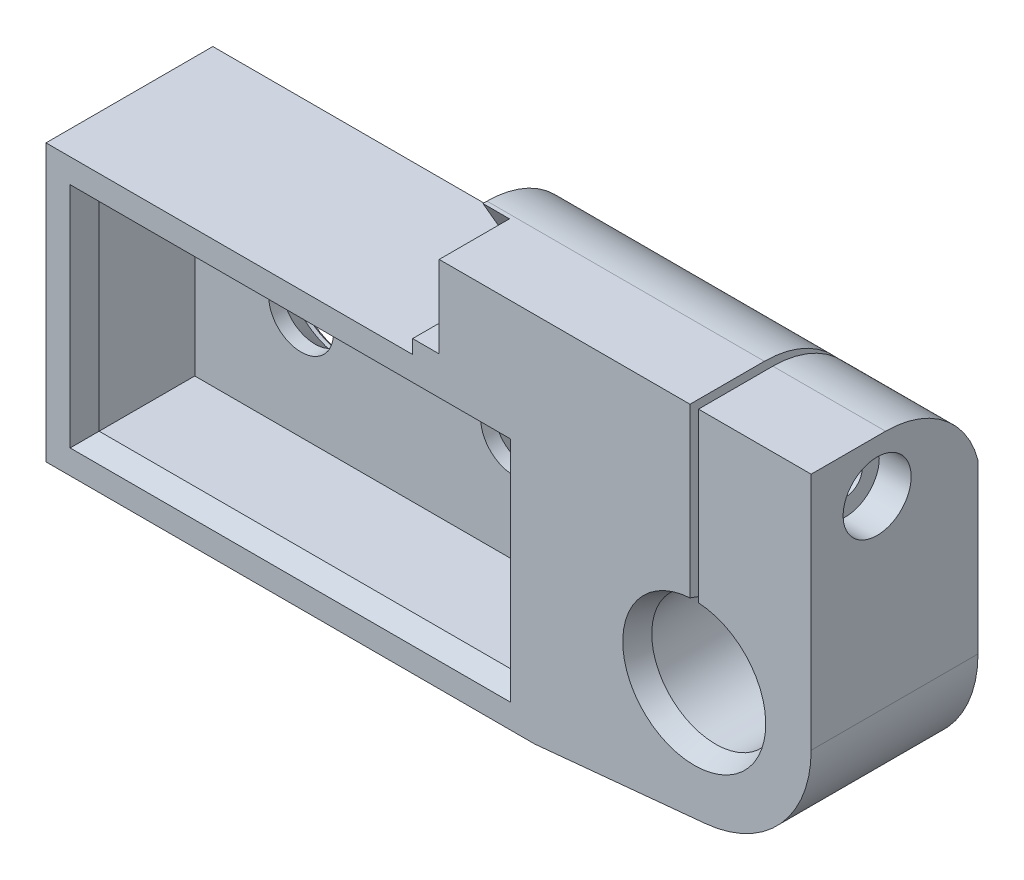
SolidWorks part; units mm, degrees
material "Custom Plastic"
ref_plane "Front Plane" through (0, 0, 0) normal (0, 0, 1) x (1, 0, 0)
ref_plane "Top Plane" through (0, 0, 0) normal (0, 1, 0) x (1, 0, 0)
ref_plane "Right Plane" through (0, 0, 0) normal (1, 0, 0) x (0, 0, -1)
sketch "Sketch1" plane through (0, 0, 0) normal (0, 0, 1) x (1, 0, 0)
  line L0 (-58, 10.5) -> (-18, -9.5) construction
  line L1 (-18, 10.5) -> (-58, 10.5) construction
  line L2 (-18, 10.5) -> (-18, -9.5) construction
  line L3 (-18, -9.5) -> (-58, -9.5) construction
  line L4 (-58, 10.5) -> (-58, -9.5) construction
  line L5 (-58, -9.5) -> (-18, 10.5) construction
  line L6 (-61, 13.5) -> (-61, -12.5)
  line L7 (-15, 13.5) -> (-61, 13.5) construction
  line L8 (-15, 13.5) -> (1.7126, 10.8659) construction
  line L10 (-48, 0.5) -> (-28, 0.5) construction
  line L11 (-61, -12.5) -> (-15, -12.5)
  line L12 (-15, -12.5) -> (-61, -12.5) construction
  line L13 (-15, 13.5) -> (-15, -12.5) construction
  line L14 (-15, -12.5) -> (1.0575, -10.949)
  line L15 (11, 0) -> (11, 22.5)
  line L16 (11, 22.5) -> (-26.5, 22.5)
  line L17 (-61, 13.5) -> (-26.5, 13.5)
  line L18 (-26.5, 13.5) -> (-26.5, 22.5)
  circle A0 centre (0, 0) radius 6 construction
  arc A1 (1.0575, -10.949) -> (11, 0) centre (0, 0) ccw
  circle A2 centre (-48, 0.5) radius 2.5
  circle A3 centre (-28, 0.5) radius 3.1
  point P11 (0, 0)
  point P12 (-38, 0.5)
  point P13 (9.6881, 0)
  dimension "D3" = 12
  dimension "D4" = 5
  dimension "D8" = 5
  dimension "D10" = 6.2
  dimension "D2" = 20
  dimension "D5" = 38
  dimension "D6" = 0.5
  dimension "D7" = 40
  dimension "D9" = 20
  dimension "D11" = 9
  dimension "D12" = 37.5
  dimension "D1" = 3
extrude "Boss-Extrude1" add sketch "Sketch1" along normal blind 16
sketch "Sketch2" plane through (0, 0, 16) normal (0, 0, 1) x (1, 0, 0)
  line L0 (-61, 13.5) -> (-61, -12.5) construction
  line L1 (-58, 10.5) -> (-18, 10.5)
  line L2 (-58, 10.5) -> (-58, -9.5)
  line L3 (-58, -9.5) -> (-18, -9.5)
  line L4 (-18, 10.5) -> (-18, -9.5)
  line L6 (-61, -12.5) -> (-15, -12.5) construction
  dimension "D1" = 3
  dimension "D2" = 3
  dimension "D3" = 20
  dimension "D4" = 40
extrude "Cut-Extrude1" cut sketch "Sketch2" against normal offset from surface (11 mm away) 5 up to face at (-45.5, 0.5, 0)
fillet "Fillet2" radius 9 1 edges at (-7.75, 22.5, 0)
sketch "Sketch3" plane through (0, 0, 16) normal (0, 0, 1) x (1, 0, 0)
  circle A0 centre (0, 0) radius 6
  dimension "D1" = 12
extrude "Cut-Extrude2" cut sketch "Sketch3" against normal offset from surface (13.5 mm away) 2.5 up to face at (-45.5, 0.5, 0)
sketch "Sketch6" plane through (0, 0, 16) normal (0, 0, 1) x (1, 0, 0)
  line L9 (-0.4, 24.3347) -> (0.4, 24.3347)
  line L10 (-0.4, 24.3347) -> (-0.4, 2.9732)
  line L15 (0.4, 24.3347) -> (0.4, 2.9732)
  line L16 (-0.4, 24.3347) -> (0.4, 2.9732) construction
  line L17 (-0.4, 2.9732) -> (0.4, 24.3347) construction
  arc A1 (-0.4, 2.9732) -> (0.4, 2.9732) centre (0, 0) ccw
  point P3 (0.1507, 0.3705)
  point P6 (0, 13.6539)
  point P7 (-14.5521, 6.3495)
  point P9 (-0.1507, -0.3705)
  point P10 (-15.3521, 5.8112)
  dimension "D4" = 3
  dimension "D3" = 0.8
extrude "Cut-Extrude5" cut sketch "Sketch6" against normal through all
sketch "Sketch7" plane through (0, 0, 0) normal (0, 0, -1) x (-1, 0, 0)
  line L0 (38, 10.5) -> (58, -9.5) construction
  line L1 (58, 10.5) -> (48, 0.5) construction
  line L3 (58, 10.5) -> (18, 10.5) construction
  circle A0 centre (48, 0.5) radius 3.05
  dimension "D1" = 6.1
extrude "Cut-Extrude6" cut sketch "Sketch7" against normal through all
sketch "Sketch8" plane through (0, 0, 16) normal (0, 0, 1) x (1, 0, 0)
  line L0 (-51.5, 9.5) -> (-44.5, 9.5) construction
  line L1 (-48, 9.5) -> (-48, 0.5) construction
  line L2 (-58, 10.5) -> (-18, 10.5) construction
  line L3 (-18, 10.5) -> (-58, 10.5) construction
  line L4 (-48, 12.2222) -> (-51.8111, 8.4111)
  line L5 (-51.8111, 8.4111) -> (-48, 4.6)
  line L6 (-48, 4.6) -> (-44.1889, 8.4111)
  line L7 (-44.1889, 8.4111) -> (-48, 12.2222)
  circle A0 centre (-51.5, 9.5) radius 0.55 construction
  circle A1 centre (-44.5, 9.5) radius 0.55 construction
  circle A2 centre (-48, 8.4111) radius 2.6948 construction
  dimension "D1" = 1.1
  dimension "D2" = 7
  dimension "D3" = 1
  dimension "D4" = 5.9
extrude "Boss-Extrude2" [suppressed] add sketch "Sketch8" against normal up to next
ref_axis "Axis1" through (-48, 0.5, 5) along (0, 0, -1)
pattern_circular "CirPattern1" [suppressed] count 2 over 360 about axis through (-48, 0.5, 5) along (0, 0, -1) of bodies 108
fillet "Fillet1" [suppressed] radius 0.8
chamfer "Chamfer2" distance 2 angle 20 4 edges at (-18, 0.5, 16) (-38, 10.5, 16) (-58, 0.5, 16) (-38, -9.5, 16) first distance on face at (-18, 0.5, 10.5) first distance on face at (-38, 10.5, 10.5) first distance on face at (-58, 0.5, 10.5) first distance on face at (-38, -9.5, 10.5)
sketch "Sketch10" plane through (0, 0, 0) normal (0, 0, -1) x (-1, 0, 0)
  circle A0 centre (28, 0.5) radius 6.1
  circle A1 centre (48, 0.5) radius 6.1
  dimension "D1" = 12.2
extrude "Cut-Extrude8" cut sketch "Sketch10" against normal blind 0.7
chamfer "Chamfer3" distance 3 angle 45 2 edges at (-51.05, 0.5, 0.7) (-31.1, 0.5, 0.7)
chamfer "Chamfer4" distance 0.3 angle 45 11 edges at (0, -3, 0) (-61, 0.5, 0) (-38, -12.5, 0) (-6.9712, -11.7245, 0) (8.1435, -7.3948, 0) (-34.1, 0.5, 0) (-54.1, 0.5, 0) (0.4, 8.2366, 0) (-0.4, 8.2366, 0) (11, 6.75, 0) (-43.75, 13.5, 0) tangent propagation no
sketch "Sketch11" plane through (11, 0, 0) normal (1, 0, 0) x (0, 0, -1)
  line L1 (-16, 13.5) -> (-0.3, 13.5) construction
  circle A0 centre (-9.7903, 17.6) radius 1.6
  circle A1 centre (-9.7903, 17.6) radius 3.1 construction
  point P3 (-9.7903, 14.5)
  dimension "D1" = 3.2
  dimension "D2" = 6.2
  dimension "D3" = 1
extrude "Cut-Extrude9" cut sketch "Sketch11" against normal through all
sketch "Sketch12" plane through (11, 0, 0) normal (1, 0, 0) x (0, 0, -1)
  circle A0 centre (-9.7903, 17.6) radius 3.2
  dimension "D1" = 6.4
extrude "Cut-Extrude10" cut sketch "Sketch12" against normal blind 3
sketch "Sketch13" plane through (11, 0, 0) normal (1, 0, 0) x (0, 0, -1)
  line L0 (-9.3862, 22.5) -> (-16, 22.5)
  line L1 (-6.5571, 17.6) -> (-9.3862, 22.5)
  line L2 (-8.2925, 20.4) -> (-11.4069, 20.4) construction
  line L3 (-11.4069, 20.4) -> (-13.0235, 17.6) construction
  line L4 (-13.0235, 17.6) -> (-11.3764, 14.7471) construction
  line L5 (-16, 14.8) -> (-8.1737, 14.8)
  line L6 (-8.1737, 14.8) -> (-6.5571, 17.6)
  line L8 (-16, 22.5) -> (-16, 14.8)
  line L10 (-16, 0) -> (-16, 22.5) construction
  line L11 (-16, 22.5) -> (-9, 22.5) construction
  circle A0 centre (-9.7903, 17.6) radius 2.8 construction
  dimension "D1" = 5.6
extrude "Cut-Extrude11" cut sketch "Sketch13" against normal through all from offset 35 offset against normal yes
chamfer "Chamfer5" distance 2 angle 20 1 edges at (0, -6, 16) first distance on face at (0, -0.0067, 9.25)
sketch "Sketch14" plane through (11, 0, 0) normal (1, 0, 0) x (0, 0, -1)
  line L0 (-9.7903, 17.6) -> (-10.9217, 18.7314)
  line L1 (-10.9217, 18.7314) -> (-11.7103, 17.9427)
  line L2 (-11.7103, 17.9427) -> (-11.7103, 17.2573)
  line L3 (-11.7103, 17.2573) -> (-10.9217, 16.4686)
  line L4 (-10.9217, 16.4686) -> (-9.7903, 17.6)
  circle A0 centre (-9.7903, 17.6) radius 1.6 construction
  point P8 (-11.3903, 17.6)
  dimension "D1" = 0.32
extrude "Cut-Extrude12" cut sketch "Sketch14" against normal through all
